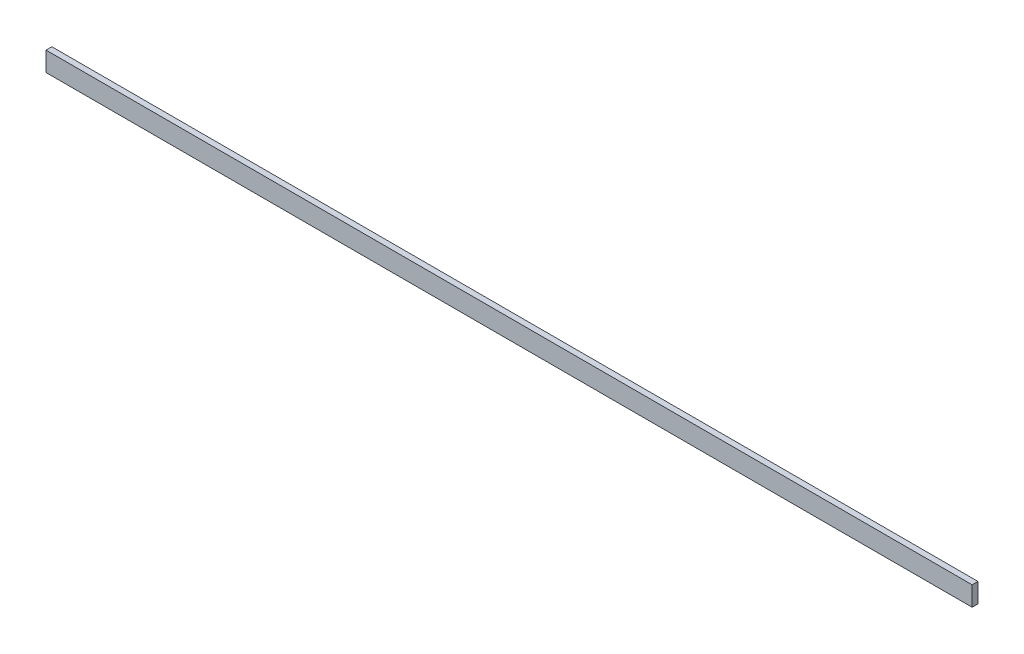
SolidWorks part; units mm, degrees
ref_plane "Ön Düzlem" through (0, 0, 0) normal (0, 0, 1) x (1, 0, 0)
ref_plane "Üst Düzlem" through (0, 0, 0) normal (0, 1, 0) x (1, 0, 0)
ref_plane "Sağ Düzlem" through (0, 0, 0) normal (1, 0, 0) x (0, 0, -1)
sketch "Çizim1" plane through (0, 0, 0) normal (0, 0, 1) x (1, 0, 0)
  line L1 (0, 0) -> (2380, 0)
  line L2 (0, 0) -> (0, -50)
  line L3 (0, -50) -> (2380, -50)
  line L4 (2380, 0) -> (2380, -50)
  dimension "D1" = 50
  dimension "D2" = 2380
base flange "Taban-Flanş1" sketch "Çizim1" thickness 15 reverse thickness direction no parameters "D1"=2.5
sketch "Büküm-Çizgileri1" [suppressed] plane through (0, 0, 0) normal (0, 1, 0) x (1, 0, 0)
sketch "Sınırlandırma-Kutusu1" [suppressed] plane through (0, 0, 0) normal (0, 1, 0) x (1, 0, 0)
sheet metal parameters "Sac-Levha1" thickness 15 parameters "D1"=2.5
flat pattern "Düz-Çoğaltma1" [suppressed]
sketch "Büküm-Çizgileri2" plane through (0, 0, 0) normal (0, 1, 0) x (1, 0, 0)
sketch3d "Sınırlandırma-Kutusu2" [suppressed]
  line L0 (0, -50, 0) -> (2380, -50, 0) construction
  line L1 (0, 0, 0) -> (2380, 0, 0) construction
  line L2 (0, -50, 0) -> (0, 0, 0) construction
  line L3 (2380, -50, 0) -> (2380, 0, 0) construction
